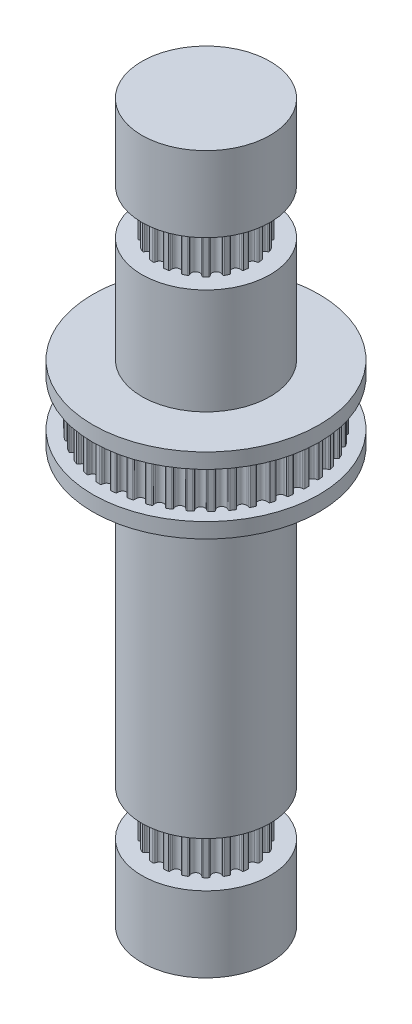
SolidWorks part; units mm, degrees
ref_plane "Front Plane" through (0, 0, 0) normal (0, 0, 1) x (1, 0, 0)
ref_plane "Top Plane" through (0, 0, 0) normal (0, 1, 0) x (1, 0, 0)
ref_plane "Right Plane" through (0, 0, 0) normal (1, 0, 0) x (0, 0, -1)
sketch "Sketch2" plane through (0, 0, 0) normal (0, 1, 0) x (1, 0, 0)
  arc A0 (-0.7447, 13.3442) -> (0.7447, 13.3442) centre (0, 0) ccw
  arc A1 (-0.5031, 12.9334) -> (0.5031, 12.9334) centre (0, 13.17) ccw
  arc A2 (0.5031, 12.9334) -> (0.5879, 13.2159) centre (-0.4018, 13.359) ccw
  arc A3 (-0.5879, 13.2159) -> (-0.5031, 12.9334) centre (0.4018, 13.359) ccw
  arc A4 (-0.7447, 13.3442) -> (-0.5879, 13.2159) centre (-0.7364, 13.1945) cw
  arc A5 (0.7447, 13.3442) -> (0.5879, 13.2159) centre (0.7364, 13.1945) ccw
  arc A6 (1.2524, 13.3062) -> (1.3884, 13.1559) centre (1.2384, 13.1568) cw
  arc A7 (1.3884, 13.1559) -> (1.4301, 12.8639) centre (2.3883, 13.1499) ccw
  arc A8 (1.4301, 12.8639) -> (2.4251, 12.7139) centre (1.9629, 13.0229) ccw
  arc A9 (2.4251, 12.7139) -> (2.5511, 12.9807) centre (1.5938, 13.2696) ccw
  arc A10 (2.7253, 13.0842) -> (2.5511, 12.9807) centre (2.6947, 12.9373) ccw
  arc A11 (3.2216, 12.9709) -> (3.3336, 12.8021) centre (3.1855, 12.8253) cw
  arc A12 (3.3336, 12.8021) -> (3.3314, 12.5071) centre (4.3216, 12.647) ccw
  arc A13 (3.3314, 12.5071) -> (4.293, 12.2105) centre (3.8819, 12.5849) ccw
  arc A14 (4.293, 12.2105) -> (4.4573, 12.4555) centre (3.5537, 12.8839) ccw
  arc A15 (4.6449, 12.5319) -> (4.4573, 12.4555) centre (4.5928, 12.3912) ccw
  arc A16 (5.1188, 12.3459) -> (5.2045, 12.1622) centre (5.0614, 12.2073) cw
  arc A17 (5.2045, 12.1622) -> (5.1583, 11.8709) centre (6.1582, 11.8617) ccw
  arc A18 (5.1583, 11.8709) -> (6.0649, 11.4343) centre (5.7142, 11.8658) ccw
  arc A19 (6.0649, 11.4343) -> (6.2639, 11.652) centre (5.4342, 12.2103) ccw
  arc A20 (6.4608, 11.6996) -> (6.2639, 11.652) centre (6.3883, 11.5683) ccw
  arc A21 (6.9017, 11.4451) -> (6.959, 11.2507) centre (6.8243, 11.3166) cw
  arc A22 (6.959, 11.2507) -> (6.8699, 10.9695) centre (7.8573, 10.8114) ccw
  arc A23 (6.8699, 10.9695) -> (7.7013, 10.4026) centre (7.4189, 10.8816) ccw
  arc A24 (7.7013, 10.4026) -> (7.9306, 10.5883) centre (7.1934, 11.264) ccw
  arc A25 (8.1324, 10.606) -> (7.9306, 10.5883) centre (8.0411, 10.487) ccw
  arc A26 (8.5304, 10.2886) -> (8.5581, 10.0879) centre (8.4347, 10.1731) cw
  arc A27 (8.5581, 10.0879) -> (8.4281, 9.8231) centre (9.3809, 9.5195) ccw
  arc A28 (8.4281, 9.8231) -> (9.1658, 9.1386) centre (8.9579, 9.6543) ccw
  arc A29 (9.1658, 9.1386) -> (9.4201, 9.2881) centre (8.7919, 10.0661) ccw
  arc A30 (9.6223, 9.2755) -> (9.4201, 9.2881) centre (9.5143, 9.1714) ccw
  arc A31 (9.9686, 8.9023) -> (9.9661, 8.6997) centre (9.8567, 8.8023) cw
  arc A32 (9.9661, 8.6997) -> (9.798, 8.4572) centre (10.695, 8.015) ccw
  arc A33 (9.798, 8.4572) -> (10.4254, 7.6705) centre (10.2967, 8.2114) ccw
  arc A34 (10.4254, 7.6705) -> (10.6992, 7.7803) centre (10.1939, 8.6433) ccw
  arc A35 (10.8973, 7.7377) -> (10.6992, 7.7803) centre (10.775, 7.6509) ccw
  arc A36 (11.1841, 7.3171) -> (11.1514, 7.1171) centre (11.0585, 7.235) cw
  arc A37 (11.1514, 7.1171) -> (10.9491, 6.9024) centre (11.7701, 6.3315) ccw
  arc A38 (10.9491, 6.9024) -> (11.4522, 6.031) centre (11.4056, 6.585) ccw
  arc A39 (11.4522, 6.031) -> (11.7393, 6.0988) centre (11.3683, 7.0274) ccw
  arc A40 (11.9288, 6.0271) -> (11.7393, 6.0988) centre (11.7949, 5.9595) ccw
  arc A41 (12.1497, 5.5685) -> (12.0876, 5.3756) centre (12.0133, 5.506) cw
  arc A42 (12.0876, 5.3756) -> (11.8555, 5.1934) centre (12.5823, 4.5066) ccw
  arc A43 (11.8555, 5.1934) -> (12.2232, 4.2567) centre (12.2596, 4.8115) ccw
  arc A44 (12.2232, 4.2567) -> (12.5172, 4.281) centre (12.2887, 5.2546) ccw
  arc A45 (12.6939, 4.1819) -> (12.5172, 4.281) centre (12.5514, 4.135) ccw
  arc A46 (12.8439, 3.6954) -> (12.7537, 3.514) centre (12.6998, 3.654) cw
  arc A47 (12.7537, 3.514) -> (12.4972, 3.3685) centre (13.1134, 2.5809) ccw
  arc A48 (12.4972, 3.3685) -> (12.7211, 2.3874) centre (12.8398, 2.9306) ccw
  arc A49 (12.7211, 2.3874) -> (13.0154, 2.3676) centre (12.9346, 3.3644) ccw
  arc A50 (13.1754, 2.2433) -> (13.0154, 2.3676) centre (13.0275, 2.2181) ccw
  arc A51 (13.2513, 1.7399) -> (13.135, 1.5739) centre (13.1025, 1.7204) cw
  arc A52 (13.135, 1.5739) -> (12.8596, 1.4682) centre (13.3516, 0.5977) ccw
  arc A53 (12.8596, 1.4682) -> (12.9348, 0.4648) centre (13.1332, 0.9842) ccw
  arc A54 (12.9348, 0.4648) -> (13.2229, 0.4013) centre (13.2916, 1.399) ccw
  arc A55 (13.3626, 0.2545) -> (13.2229, 0.4013) centre (13.2126, 0.2517) ccw
  arc A56 (13.3626, -0.2545) -> (13.2229, -0.4013) centre (13.2126, -0.2517) cw
  arc A57 (13.2229, -0.4013) -> (12.9348, -0.4648) centre (13.2916, -1.399) ccw
  arc A58 (12.9348, -0.4648) -> (12.8596, -1.4682) centre (13.1332, -0.9842) ccw
  arc A59 (12.8596, -1.4682) -> (13.135, -1.5739) centre (13.3516, -0.5977) ccw
  arc A60 (13.2513, -1.7399) -> (13.135, -1.5739) centre (13.1025, -1.7204) ccw
  arc A61 (13.1754, -2.2433) -> (13.0154, -2.3676) centre (13.0275, -2.2181) cw
  arc A62 (13.0154, -2.3676) -> (12.7211, -2.3874) centre (12.9346, -3.3644) ccw
  arc A63 (12.7211, -2.3874) -> (12.4972, -3.3685) centre (12.8398, -2.9306) ccw
  arc A64 (12.4972, -3.3685) -> (12.7537, -3.514) centre (13.1134, -2.5809) ccw
  arc A65 (12.8439, -3.6954) -> (12.7537, -3.514) centre (12.6998, -3.654) ccw
  arc A66 (12.6939, -4.1819) -> (12.5172, -4.281) centre (12.5514, -4.135) cw
  arc A67 (12.5172, -4.281) -> (12.2232, -4.2567) centre (12.2887, -5.2546) ccw
  arc A68 (12.2232, -4.2567) -> (11.8555, -5.1934) centre (12.2596, -4.8115) ccw
  arc A69 (11.8555, -5.1934) -> (12.0876, -5.3756) centre (12.5823, -4.5066) ccw
  arc A70 (12.1497, -5.5685) -> (12.0876, -5.3756) centre (12.0133, -5.506) ccw
  arc A71 (11.9288, -6.0271) -> (11.7393, -6.0988) centre (11.7949, -5.9595) cw
  arc A72 (11.7393, -6.0988) -> (11.4522, -6.031) centre (11.3683, -7.0274) ccw
  arc A73 (11.4522, -6.031) -> (10.9491, -6.9024) centre (11.4056, -6.585) ccw
  arc A74 (10.9491, -6.9024) -> (11.1514, -7.1171) centre (11.7701, -6.3315) ccw
  arc A75 (11.1841, -7.3171) -> (11.1514, -7.1171) centre (11.0585, -7.235) ccw
  arc A76 (10.8973, -7.7377) -> (10.6992, -7.7803) centre (10.775, -7.6509) cw
  arc A77 (10.6992, -7.7803) -> (10.4254, -7.6705) centre (10.1939, -8.6433) ccw
  arc A78 (10.4254, -7.6705) -> (9.798, -8.4572) centre (10.2967, -8.2114) ccw
  arc A79 (9.798, -8.4572) -> (9.9661, -8.6997) centre (10.695, -8.015) ccw
  arc A80 (9.9686, -8.9023) -> (9.9661, -8.6997) centre (9.8567, -8.8023) ccw
  arc A81 (9.6223, -9.2755) -> (9.4201, -9.2881) centre (9.5143, -9.1714) cw
  arc A82 (9.4201, -9.2881) -> (9.1658, -9.1386) centre (8.7919, -10.0661) ccw
  arc A83 (9.1658, -9.1386) -> (8.4281, -9.8231) centre (8.9579, -9.6543) ccw
  arc A84 (8.4281, -9.8231) -> (8.5581, -10.0879) centre (9.3809, -9.5195) ccw
  arc A85 (8.5304, -10.2886) -> (8.5581, -10.0879) centre (8.4347, -10.1731) ccw
  arc A86 (8.1324, -10.606) -> (7.9306, -10.5883) centre (8.0411, -10.487) cw
  arc A87 (7.9306, -10.5883) -> (7.7013, -10.4026) centre (7.1934, -11.264) ccw
  arc A88 (7.7013, -10.4026) -> (6.8699, -10.9695) centre (7.4189, -10.8816) ccw
  arc A89 (6.8699, -10.9695) -> (6.959, -11.2507) centre (7.8573, -10.8114) ccw
  arc A90 (6.9017, -11.4451) -> (6.959, -11.2507) centre (6.8243, -11.3166) ccw
  arc A91 (6.4608, -11.6996) -> (6.2639, -11.652) centre (6.3883, -11.5683) cw
  arc A92 (6.2639, -11.652) -> (6.0649, -11.4343) centre (5.4342, -12.2103) ccw
  arc A93 (6.0649, -11.4343) -> (5.1583, -11.8709) centre (5.7142, -11.8658) ccw
  arc A94 (5.1583, -11.8709) -> (5.2045, -12.1622) centre (6.1582, -11.8617) ccw
  arc A95 (5.1188, -12.3459) -> (5.2045, -12.1622) centre (5.0614, -12.2073) ccw
  arc A96 (4.6449, -12.5319) -> (4.4573, -12.4555) centre (4.5928, -12.3912) cw
  arc A97 (4.4573, -12.4555) -> (4.293, -12.2105) centre (3.5537, -12.8839) ccw
  arc A98 (4.293, -12.2105) -> (3.3314, -12.5071) centre (3.8819, -12.5849) ccw
  arc A99 (3.3314, -12.5071) -> (3.3336, -12.8021) centre (4.3216, -12.647) ccw
  arc A100 (3.2216, -12.9709) -> (3.3336, -12.8021) centre (3.1855, -12.8253) ccw
  arc A101 (2.7253, -13.0842) -> (2.5511, -12.9807) centre (2.6947, -12.9373) cw
  arc A102 (2.5511, -12.9807) -> (2.4251, -12.7139) centre (1.5938, -13.2696) ccw
  arc A103 (2.4251, -12.7139) -> (1.4301, -12.8639) centre (1.9629, -13.0229) ccw
  arc A104 (1.4301, -12.8639) -> (1.3884, -13.1559) centre (2.3883, -13.1499) ccw
  arc A105 (1.2524, -13.3062) -> (1.3884, -13.1559) centre (1.2384, -13.1568) ccw
  arc A106 (0.7447, -13.3442) -> (0.5879, -13.2159) centre (0.7364, -13.1945) cw
  arc A107 (0.5879, -13.2159) -> (0.5031, -12.9334) centre (-0.4018, -13.359) ccw
  arc A108 (0.5031, -12.9334) -> (-0.5031, -12.9334) centre (0, -13.17) ccw
  arc A109 (-0.5031, -12.9334) -> (-0.5879, -13.2159) centre (0.4018, -13.359) ccw
  arc A110 (-0.7447, -13.3442) -> (-0.5879, -13.2159) centre (-0.7364, -13.1945) ccw
  arc A111 (-1.2524, -13.3062) -> (-1.3884, -13.1559) centre (-1.2384, -13.1568) cw
  arc A112 (-1.3884, -13.1559) -> (-1.4301, -12.8639) centre (-2.3883, -13.1499) ccw
  arc A113 (-1.4301, -12.8639) -> (-2.4251, -12.7139) centre (-1.9629, -13.0229) ccw
  arc A114 (-2.4251, -12.7139) -> (-2.5511, -12.9807) centre (-1.5938, -13.2696) ccw
  arc A115 (-2.7253, -13.0842) -> (-2.5511, -12.9807) centre (-2.6947, -12.9373) ccw
  arc A116 (-3.2216, -12.9709) -> (-3.3336, -12.8021) centre (-3.1855, -12.8253) cw
  arc A117 (-3.3336, -12.8021) -> (-3.3314, -12.5071) centre (-4.3216, -12.647) ccw
  arc A118 (-3.3314, -12.5071) -> (-4.293, -12.2105) centre (-3.8819, -12.5849) ccw
  arc A119 (-4.293, -12.2105) -> (-4.4573, -12.4555) centre (-3.5537, -12.8839) ccw
  arc A120 (-4.6449, -12.5319) -> (-4.4573, -12.4555) centre (-4.5928, -12.3912) ccw
  arc A121 (-5.1188, -12.3459) -> (-5.2045, -12.1622) centre (-5.0614, -12.2073) cw
  arc A122 (-5.2045, -12.1622) -> (-5.1583, -11.8709) centre (-6.1582, -11.8617) ccw
  arc A123 (-5.1583, -11.8709) -> (-6.0649, -11.4343) centre (-5.7142, -11.8658) ccw
  arc A124 (-6.0649, -11.4343) -> (-6.2639, -11.652) centre (-5.4342, -12.2103) ccw
  arc A125 (-6.4608, -11.6996) -> (-6.2639, -11.652) centre (-6.3883, -11.5683) ccw
  arc A126 (-6.9017, -11.4451) -> (-6.959, -11.2507) centre (-6.8243, -11.3166) cw
  arc A127 (-6.959, -11.2507) -> (-6.8699, -10.9695) centre (-7.8573, -10.8114) ccw
  arc A128 (-6.8699, -10.9695) -> (-7.7013, -10.4026) centre (-7.4189, -10.8816) ccw
  arc A129 (-7.7013, -10.4026) -> (-7.9306, -10.5883) centre (-7.1934, -11.264) ccw
  arc A130 (-8.1324, -10.606) -> (-7.9306, -10.5883) centre (-8.0411, -10.487) ccw
  arc A131 (-8.5304, -10.2886) -> (-8.5581, -10.0879) centre (-8.4347, -10.1731) cw
  arc A132 (-8.5581, -10.0879) -> (-8.4281, -9.8231) centre (-9.3809, -9.5195) ccw
  arc A133 (-8.4281, -9.8231) -> (-9.1658, -9.1386) centre (-8.9579, -9.6543) ccw
  arc A134 (-9.1658, -9.1386) -> (-9.4201, -9.2881) centre (-8.7919, -10.0661) ccw
  arc A135 (-9.6223, -9.2755) -> (-9.4201, -9.2881) centre (-9.5143, -9.1714) ccw
  arc A136 (-9.9686, -8.9023) -> (-9.9661, -8.6997) centre (-9.8567, -8.8023) cw
  arc A137 (-9.9661, -8.6997) -> (-9.798, -8.4572) centre (-10.695, -8.015) ccw
  arc A138 (-9.798, -8.4572) -> (-10.4254, -7.6705) centre (-10.2967, -8.2114) ccw
  arc A139 (-10.4254, -7.6705) -> (-10.6992, -7.7803) centre (-10.1939, -8.6433) ccw
  arc A140 (-10.8973, -7.7377) -> (-10.6992, -7.7803) centre (-10.775, -7.6509) ccw
  arc A141 (-11.1841, -7.3171) -> (-11.1514, -7.1171) centre (-11.0585, -7.235) cw
  arc A142 (-11.1514, -7.1171) -> (-10.9491, -6.9024) centre (-11.7701, -6.3315) ccw
  arc A143 (-10.9491, -6.9024) -> (-11.4522, -6.031) centre (-11.4056, -6.585) ccw
  arc A144 (-11.4522, -6.031) -> (-11.7393, -6.0988) centre (-11.3683, -7.0274) ccw
  arc A145 (-11.9288, -6.0271) -> (-11.7393, -6.0988) centre (-11.7949, -5.9595) ccw
  arc A146 (-12.1497, -5.5685) -> (-12.0876, -5.3756) centre (-12.0133, -5.506) cw
  arc A147 (-12.0876, -5.3756) -> (-11.8555, -5.1934) centre (-12.5823, -4.5066) ccw
  arc A148 (-11.8555, -5.1934) -> (-12.2232, -4.2567) centre (-12.2596, -4.8115) ccw
  arc A149 (-12.2232, -4.2567) -> (-12.5172, -4.281) centre (-12.2887, -5.2546) ccw
  arc A150 (-12.6939, -4.1819) -> (-12.5172, -4.281) centre (-12.5514, -4.135) ccw
  arc A151 (-12.8439, -3.6954) -> (-12.7537, -3.514) centre (-12.6998, -3.654) cw
  arc A152 (-12.7537, -3.514) -> (-12.4972, -3.3685) centre (-13.1134, -2.5809) ccw
  arc A153 (-12.4972, -3.3685) -> (-12.7211, -2.3874) centre (-12.8398, -2.9306) ccw
  arc A154 (-12.7211, -2.3874) -> (-13.0154, -2.3676) centre (-12.9346, -3.3644) ccw
  arc A155 (-13.1754, -2.2433) -> (-13.0154, -2.3676) centre (-13.0275, -2.2181) ccw
  arc A156 (-13.2513, -1.7399) -> (-13.135, -1.5739) centre (-13.1025, -1.7204) cw
  arc A157 (-13.135, -1.5739) -> (-12.8596, -1.4682) centre (-13.3516, -0.5977) ccw
  arc A158 (-12.8596, -1.4682) -> (-12.9348, -0.4648) centre (-13.1332, -0.9842) ccw
  arc A159 (-12.9348, -0.4648) -> (-13.2229, -0.4013) centre (-13.2916, -1.399) ccw
  arc A160 (-13.3626, -0.2545) -> (-13.2229, -0.4013) centre (-13.2126, -0.2517) ccw
  arc A161 (-13.3626, 0.2545) -> (-13.2229, 0.4013) centre (-13.2126, 0.2517) cw
  arc A162 (-13.2229, 0.4013) -> (-12.9348, 0.4648) centre (-13.2916, 1.399) ccw
  arc A163 (-12.9348, 0.4648) -> (-12.8596, 1.4682) centre (-13.1332, 0.9842) ccw
  arc A164 (-12.8596, 1.4682) -> (-13.135, 1.5739) centre (-13.3516, 0.5977) ccw
  arc A165 (-13.2513, 1.7399) -> (-13.135, 1.5739) centre (-13.1025, 1.7204) ccw
  arc A166 (-13.1754, 2.2433) -> (-13.0154, 2.3676) centre (-13.0275, 2.2181) cw
  arc A167 (-13.0154, 2.3676) -> (-12.7211, 2.3874) centre (-12.9346, 3.3644) ccw
  arc A168 (-12.7211, 2.3874) -> (-12.4972, 3.3685) centre (-12.8398, 2.9306) ccw
  arc A169 (-12.4972, 3.3685) -> (-12.7537, 3.514) centre (-13.1134, 2.5809) ccw
  arc A170 (-12.8439, 3.6954) -> (-12.7537, 3.514) centre (-12.6998, 3.654) ccw
  arc A171 (-12.6939, 4.1819) -> (-12.5172, 4.281) centre (-12.5514, 4.135) cw
  arc A172 (-12.5172, 4.281) -> (-12.2232, 4.2567) centre (-12.2887, 5.2546) ccw
  arc A173 (-12.2232, 4.2567) -> (-11.8555, 5.1934) centre (-12.2596, 4.8115) ccw
  arc A174 (-11.8555, 5.1934) -> (-12.0876, 5.3756) centre (-12.5823, 4.5066) ccw
  arc A175 (-12.1497, 5.5685) -> (-12.0876, 5.3756) centre (-12.0133, 5.506) ccw
  arc A176 (-11.9288, 6.0271) -> (-11.7393, 6.0988) centre (-11.7949, 5.9595) cw
  arc A177 (-11.7393, 6.0988) -> (-11.4522, 6.031) centre (-11.3683, 7.0274) ccw
  arc A178 (-11.4522, 6.031) -> (-10.9491, 6.9024) centre (-11.4056, 6.585) ccw
  arc A179 (-10.9491, 6.9024) -> (-11.1514, 7.1171) centre (-11.7701, 6.3315) ccw
  arc A180 (-11.1841, 7.3171) -> (-11.1514, 7.1171) centre (-11.0585, 7.235) ccw
  arc A181 (-10.8973, 7.7377) -> (-10.6992, 7.7803) centre (-10.775, 7.6509) cw
  arc A182 (-10.6992, 7.7803) -> (-10.4254, 7.6705) centre (-10.1939, 8.6433) ccw
  arc A183 (-10.4254, 7.6705) -> (-9.798, 8.4572) centre (-10.2967, 8.2114) ccw
  arc A184 (-9.798, 8.4572) -> (-9.9661, 8.6997) centre (-10.695, 8.015) ccw
  arc A185 (-9.9686, 8.9023) -> (-9.9661, 8.6997) centre (-9.8567, 8.8023) ccw
  arc A186 (-9.6223, 9.2755) -> (-9.4201, 9.2881) centre (-9.5143, 9.1714) cw
  arc A187 (-9.4201, 9.2881) -> (-9.1658, 9.1386) centre (-8.7919, 10.0661) ccw
  arc A188 (-9.1658, 9.1386) -> (-8.4281, 9.8231) centre (-8.9579, 9.6543) ccw
  arc A189 (-8.4281, 9.8231) -> (-8.5581, 10.0879) centre (-9.3809, 9.5195) ccw
  arc A190 (-8.5304, 10.2886) -> (-8.5581, 10.0879) centre (-8.4347, 10.1731) ccw
  arc A191 (-8.1324, 10.606) -> (-7.9306, 10.5883) centre (-8.0411, 10.487) cw
  arc A192 (-7.9306, 10.5883) -> (-7.7013, 10.4026) centre (-7.1934, 11.264) ccw
  arc A193 (-7.7013, 10.4026) -> (-6.8699, 10.9695) centre (-7.4189, 10.8816) ccw
  arc A194 (-6.8699, 10.9695) -> (-6.959, 11.2507) centre (-7.8573, 10.8114) ccw
  arc A195 (-6.9017, 11.4451) -> (-6.959, 11.2507) centre (-6.8243, 11.3166) ccw
  arc A196 (-6.4608, 11.6996) -> (-6.2639, 11.652) centre (-6.3883, 11.5683) cw
  arc A197 (-6.2639, 11.652) -> (-6.0649, 11.4343) centre (-5.4342, 12.2103) ccw
  arc A198 (-6.0649, 11.4343) -> (-5.1583, 11.8709) centre (-5.7142, 11.8658) ccw
  arc A199 (-5.1583, 11.8709) -> (-5.2045, 12.1622) centre (-6.1582, 11.8617) ccw
  arc A200 (-5.1188, 12.3459) -> (-5.2045, 12.1622) centre (-5.0614, 12.2073) ccw
  arc A201 (-4.6449, 12.5319) -> (-4.4573, 12.4555) centre (-4.5928, 12.3912) cw
  arc A202 (-4.4573, 12.4555) -> (-4.293, 12.2105) centre (-3.5537, 12.8839) ccw
  arc A203 (-4.293, 12.2105) -> (-3.3314, 12.5071) centre (-3.8819, 12.5849) ccw
  arc A204 (-3.3314, 12.5071) -> (-3.3336, 12.8021) centre (-4.3216, 12.647) ccw
  arc A205 (-3.2216, 12.9709) -> (-3.3336, 12.8021) centre (-3.1855, 12.8253) ccw
  arc A206 (-2.7253, 13.0842) -> (-2.5511, 12.9807) centre (-2.6947, 12.9373) cw
  arc A207 (-2.5511, 12.9807) -> (-2.4251, 12.7139) centre (-1.5938, 13.2696) ccw
  arc A208 (-2.4251, 12.7139) -> (-1.4301, 12.8639) centre (-1.9629, 13.0229) ccw
  arc A209 (-1.4301, 12.8639) -> (-1.3884, 13.1559) centre (-2.3883, 13.1499) ccw
  arc A210 (-1.2524, 13.3062) -> (-1.3884, 13.1559) centre (-1.2384, 13.1568) ccw
  point P5 (0, 13.365)
  point P468 (0, 0)
  dimension "D1" = 26.73
  dimension "D2" = 1.112
  dimension "D4" = 2
  dimension "D5" = 2
  dimension "D6" = 0.15
  dimension "D3" = 0.195
  dimension "D7" = 42
extrude "Boss-Extrude1" add sketch "Sketch2" along normal mid plane 10 contours A0 A210 A209 A208 A207 A206 A205 A204 A203 A202 A201 A200 A199 A198 A197 A196 A195 A194 A193 A192 A191 A190 A189 A188 A187 A186 A185 A184 A183 A182 A181 A180 A179 A178 A177 A176 A175 A174 A173 A172 A171 A170 A169 region at (0, 0, 0)
sketch "Sketch3" plane through (0, 5, 0) normal (0, 1, 0) x (1, 0, 0)
  circle A0 centre (0, 0) radius 15
  dimension "D1" = 30
extrude "Boss-Extrude2" add sketch "Sketch3" against normal blind 2
mirror "Mirror1" about plane through (0, 0, 0) normal (0, 1, 0) of "Boss-Extrude2"
sketch "Sketch4" plane through (0, 5, 0) normal (0, 1, 0) x (1, 0, 0)
  arc A0 (-0.7485, 6.3218) -> (0.7485, 6.3218) centre (0, 0) ccw
  arc A1 (-0.5071, 5.943) -> (0.5071, 5.943) centre (0, 6.171) ccw
  arc A2 (0.5071, 5.943) -> (0.5827, 6.1964) centre (-0.4049, 6.3531) ccw
  arc A3 (-0.5827, 6.1964) -> (-0.5071, 5.943) centre (0.4049, 6.3531) ccw
  arc A4 (0.7485, 6.3218) -> (0.5827, 6.1964) centre (0.7309, 6.1729) ccw
  arc A5 (-0.5827, 6.1964) -> (-0.7485, 6.3218) centre (-0.7309, 6.1729) ccw
  arc A6 (1.3606, 6.0732) -> (1.2417, 6.2437) centre (1.2124, 6.0966) ccw
  arc A7 (1.3606, 6.0732) -> (1.3542, 5.8088) centre (2.3483, 5.917) ccw
  arc A8 (1.3542, 5.8088) -> (2.3187, 5.4954) centre (1.9069, 5.869) ccw
  arc A9 (2.3187, 5.4954) -> (2.469, 5.7131) centre (1.5781, 6.1673) ccw
  arc A10 (2.6654, 5.7811) -> (2.469, 5.7131) centre (2.6026, 5.6449) ccw
  arc A11 (3.1707, 5.3555) -> (3.1103, 5.5544) centre (3.0371, 5.4236) ccw
  arc A12 (3.1707, 5.3555) -> (3.0829, 5.106) centre (4.0619, 4.9018) ccw
  arc A13 (3.0829, 5.106) -> (3.9034, 4.5099) centre (3.6272, 4.9924) ccw
  arc A14 (3.9034, 4.5099) -> (4.1136, 4.6705) centre (3.4067, 5.3778) ccw
  arc A15 (4.3214, 4.6745) -> (4.1136, 4.6705) centre (4.2196, 4.5644) ccw
  arc A16 (4.6705, 4.1136) -> (4.6745, 4.3214) centre (4.5644, 4.2196) ccw
  arc A17 (4.6705, 4.1136) -> (4.5099, 3.9034) centre (5.3778, 3.4067) ccw
  arc A18 (4.5099, 3.9034) -> (5.106, 3.0829) centre (4.9924, 3.6272) ccw
  arc A19 (5.106, 3.0829) -> (5.3555, 3.1707) centre (4.9018, 4.0619) ccw
  arc A20 (5.5544, 3.1103) -> (5.3555, 3.1707) centre (5.4236, 3.0371) ccw
  arc A21 (5.7131, 2.469) -> (5.7811, 2.6654) centre (5.6449, 2.6026) ccw
  arc A22 (5.7131, 2.469) -> (5.4954, 2.3187) centre (6.1673, 1.5781) ccw
  arc A23 (5.4954, 2.3187) -> (5.8088, 1.3542) centre (5.869, 1.9069) ccw
  arc A24 (5.8088, 1.3542) -> (6.0732, 1.3606) centre (5.917, 2.3483) ccw
  arc A25 (6.2437, 1.2417) -> (6.0732, 1.3606) centre (6.0966, 1.2124) ccw
  arc A26 (6.1964, 0.5827) -> (6.3218, 0.7485) centre (6.1729, 0.7309) ccw
  arc A27 (6.1964, 0.5827) -> (5.943, 0.5071) centre (6.3531, -0.4049) ccw
  arc A28 (5.943, 0.5071) -> (5.943, -0.5071) centre (6.171, 0) ccw
  arc A29 (5.943, -0.5071) -> (6.1964, -0.5827) centre (6.3531, 0.4049) ccw
  arc A30 (6.3218, -0.7485) -> (6.1964, -0.5827) centre (6.1729, -0.7309) ccw
  arc A31 (6.0732, -1.3606) -> (6.2437, -1.2417) centre (6.0966, -1.2124) ccw
  arc A32 (6.0732, -1.3606) -> (5.8088, -1.3542) centre (5.917, -2.3483) ccw
  arc A33 (5.8088, -1.3542) -> (5.4954, -2.3187) centre (5.869, -1.9069) ccw
  arc A34 (5.4954, -2.3187) -> (5.7131, -2.469) centre (6.1673, -1.5781) ccw
  arc A35 (5.7811, -2.6654) -> (5.7131, -2.469) centre (5.6449, -2.6026) ccw
  arc A36 (5.3555, -3.1707) -> (5.5544, -3.1103) centre (5.4236, -3.0371) ccw
  arc A37 (5.3555, -3.1707) -> (5.106, -3.0829) centre (4.9018, -4.0619) ccw
  arc A38 (5.106, -3.0829) -> (4.5099, -3.9034) centre (4.9924, -3.6272) ccw
  arc A39 (4.5099, -3.9034) -> (4.6705, -4.1136) centre (5.3778, -3.4067) ccw
  arc A40 (4.6745, -4.3214) -> (4.6705, -4.1136) centre (4.5644, -4.2196) ccw
  arc A41 (4.1136, -4.6705) -> (4.3214, -4.6745) centre (4.2196, -4.5644) ccw
  arc A42 (4.1136, -4.6705) -> (3.9034, -4.5099) centre (3.4067, -5.3778) ccw
  arc A43 (3.9034, -4.5099) -> (3.0829, -5.106) centre (3.6272, -4.9924) ccw
  arc A44 (3.0829, -5.106) -> (3.1707, -5.3555) centre (4.0619, -4.9018) ccw
  arc A45 (3.1103, -5.5544) -> (3.1707, -5.3555) centre (3.0371, -5.4236) ccw
  arc A46 (2.469, -5.7131) -> (2.6654, -5.7811) centre (2.6026, -5.6449) ccw
  arc A47 (2.469, -5.7131) -> (2.3187, -5.4954) centre (1.5781, -6.1673) ccw
  arc A48 (2.3187, -5.4954) -> (1.3542, -5.8088) centre (1.9069, -5.869) ccw
  arc A49 (1.3542, -5.8088) -> (1.3606, -6.0732) centre (2.3483, -5.917) ccw
  arc A50 (1.2417, -6.2437) -> (1.3606, -6.0732) centre (1.2124, -6.0966) ccw
  arc A51 (0.5827, -6.1964) -> (0.7485, -6.3218) centre (0.7309, -6.1729) ccw
  arc A52 (0.5827, -6.1964) -> (0.5071, -5.943) centre (-0.4049, -6.3531) ccw
  arc A53 (0.5071, -5.943) -> (-0.5071, -5.943) centre (0, -6.171) ccw
  arc A54 (-0.5071, -5.943) -> (-0.5827, -6.1964) centre (0.4049, -6.3531) ccw
  arc A55 (-0.7485, -6.3218) -> (-0.5827, -6.1964) centre (-0.7309, -6.1729) ccw
  arc A56 (-1.3606, -6.0732) -> (-1.2417, -6.2437) centre (-1.2124, -6.0966) ccw
  arc A57 (-1.3606, -6.0732) -> (-1.3542, -5.8088) centre (-2.3483, -5.917) ccw
  arc A58 (-1.3542, -5.8088) -> (-2.3187, -5.4954) centre (-1.9069, -5.869) ccw
  arc A59 (-2.3187, -5.4954) -> (-2.469, -5.7131) centre (-1.5781, -6.1673) ccw
  arc A60 (-2.6654, -5.7811) -> (-2.469, -5.7131) centre (-2.6026, -5.6449) ccw
  arc A61 (-3.1707, -5.3555) -> (-3.1103, -5.5544) centre (-3.0371, -5.4236) ccw
  arc A62 (-3.1707, -5.3555) -> (-3.0829, -5.106) centre (-4.0619, -4.9018) ccw
  arc A63 (-3.0829, -5.106) -> (-3.9034, -4.5099) centre (-3.6272, -4.9924) ccw
  arc A64 (-3.9034, -4.5099) -> (-4.1136, -4.6705) centre (-3.4067, -5.3778) ccw
  arc A65 (-4.3214, -4.6745) -> (-4.1136, -4.6705) centre (-4.2196, -4.5644) ccw
  arc A66 (-4.6705, -4.1136) -> (-4.6745, -4.3214) centre (-4.5644, -4.2196) ccw
  arc A67 (-4.6705, -4.1136) -> (-4.5099, -3.9034) centre (-5.3778, -3.4067) ccw
  arc A68 (-4.5099, -3.9034) -> (-5.106, -3.0829) centre (-4.9924, -3.6272) ccw
  arc A69 (-5.106, -3.0829) -> (-5.3555, -3.1707) centre (-4.9018, -4.0619) ccw
  arc A70 (-5.5544, -3.1103) -> (-5.3555, -3.1707) centre (-5.4236, -3.0371) ccw
  arc A71 (-5.7131, -2.469) -> (-5.7811, -2.6654) centre (-5.6449, -2.6026) ccw
  arc A72 (-5.7131, -2.469) -> (-5.4954, -2.3187) centre (-6.1673, -1.5781) ccw
  arc A73 (-5.4954, -2.3187) -> (-5.8088, -1.3542) centre (-5.869, -1.9069) ccw
  arc A74 (-5.8088, -1.3542) -> (-6.0732, -1.3606) centre (-5.917, -2.3483) ccw
  arc A75 (-6.2437, -1.2417) -> (-6.0732, -1.3606) centre (-6.0966, -1.2124) ccw
  arc A76 (-6.1964, -0.5827) -> (-6.3218, -0.7485) centre (-6.1729, -0.7309) ccw
  arc A77 (-6.1964, -0.5827) -> (-5.943, -0.5071) centre (-6.3531, 0.4049) ccw
  arc A78 (-5.943, -0.5071) -> (-5.943, 0.5071) centre (-6.171, 0) ccw
  arc A79 (-5.943, 0.5071) -> (-6.1964, 0.5827) centre (-6.3531, -0.4049) ccw
  arc A80 (-6.3218, 0.7485) -> (-6.1964, 0.5827) centre (-6.1729, 0.7309) ccw
  arc A81 (-6.0732, 1.3606) -> (-6.2437, 1.2417) centre (-6.0966, 1.2124) ccw
  arc A82 (-6.0732, 1.3606) -> (-5.8088, 1.3542) centre (-5.917, 2.3483) ccw
  arc A83 (-5.8088, 1.3542) -> (-5.4954, 2.3187) centre (-5.869, 1.9069) ccw
  arc A84 (-5.4954, 2.3187) -> (-5.7131, 2.469) centre (-6.1673, 1.5781) ccw
  arc A85 (-5.7811, 2.6654) -> (-5.7131, 2.469) centre (-5.6449, 2.6026) ccw
  arc A86 (-5.3555, 3.1707) -> (-5.5544, 3.1103) centre (-5.4236, 3.0371) ccw
  arc A87 (-5.3555, 3.1707) -> (-5.106, 3.0829) centre (-4.9018, 4.0619) ccw
  arc A88 (-5.106, 3.0829) -> (-4.5099, 3.9034) centre (-4.9924, 3.6272) ccw
  arc A89 (-4.5099, 3.9034) -> (-4.6705, 4.1136) centre (-5.3778, 3.4067) ccw
  arc A90 (-4.6745, 4.3214) -> (-4.6705, 4.1136) centre (-4.5644, 4.2196) ccw
  arc A91 (-4.1136, 4.6705) -> (-4.3214, 4.6745) centre (-4.2196, 4.5644) ccw
  arc A92 (-4.1136, 4.6705) -> (-3.9034, 4.5099) centre (-3.4067, 5.3778) ccw
  arc A93 (-3.9034, 4.5099) -> (-3.0829, 5.106) centre (-3.6272, 4.9924) ccw
  arc A94 (-3.0829, 5.106) -> (-3.1707, 5.3555) centre (-4.0619, 4.9018) ccw
  arc A95 (-3.1103, 5.5544) -> (-3.1707, 5.3555) centre (-3.0371, 5.4236) ccw
  arc A96 (-2.469, 5.7131) -> (-2.6654, 5.7811) centre (-2.6026, 5.6449) ccw
  arc A97 (-2.469, 5.7131) -> (-2.3187, 5.4954) centre (-1.5781, 6.1673) ccw
  arc A98 (-2.3187, 5.4954) -> (-1.3542, 5.8088) centre (-1.9069, 5.869) ccw
  arc A99 (-1.3542, 5.8088) -> (-1.3606, 6.0732) centre (-2.3483, 5.917) ccw
  arc A100 (-1.2417, 6.2437) -> (-1.3606, 6.0732) centre (-1.2124, 6.0966) ccw
  point P5 (0, 6.366)
  point P226 (0, 0)
  dimension "D1" = 12.732
  dimension "D2" = 1.112
  dimension "D4" = 2
  dimension "D5" = 2
  dimension "D6" = 0.15
  dimension "D3" = 0.195
  dimension "D7" = 20
extrude "Boss-Extrude3" add sketch "Sketch4" along normal blind 30 and the other way blind 65 contours A0 A100 A99 A98 A97 A96 A95 A94 A93 A92 A91 A90 A89 A88 A87 A86 A85 A84 A83 A82 A81 A80 A79 A78 A77 A76 A75 A74 A73 A72 A71 A70 A69 A68 A67 A66 A65 A64 A63 A62 A61 A60 A59 region at (0, 5, 0)
sketch "Sketch5" plane through (0, 35, 0) normal (0, 1, 0) x (1, 0, 0)
  circle A0 centre (0, 0) radius 8.5
  dimension "D1" = 17
extrude "Boss-Extrude4" add sketch "Sketch5" against normal blind 10
sketch "Sketch6" plane through (0, -60, 0) normal (0, -1, 0) x (1, 0, 0)
  circle A0 centre (0, 0) radius 8.5
  dimension "D1" = 17
extrude "Boss-Extrude5" add sketch "Sketch6" against normal blind 10
ref_plane "Plane1" through (0, 19, 0) normal (0, -1, 0) x (-1, 0, 0)
sketch "Sketch7" plane through (0, 19, 0) normal (0, -1, 0) x (-1, 0, 0)
  circle A0 centre (0, 0) radius 8.5
  dimension "D1" = 17
extrude "Boss-Extrude6" add sketch "Sketch7" along normal offset from surface (63 mm away) 6 up to face at (0, -50, 0)
